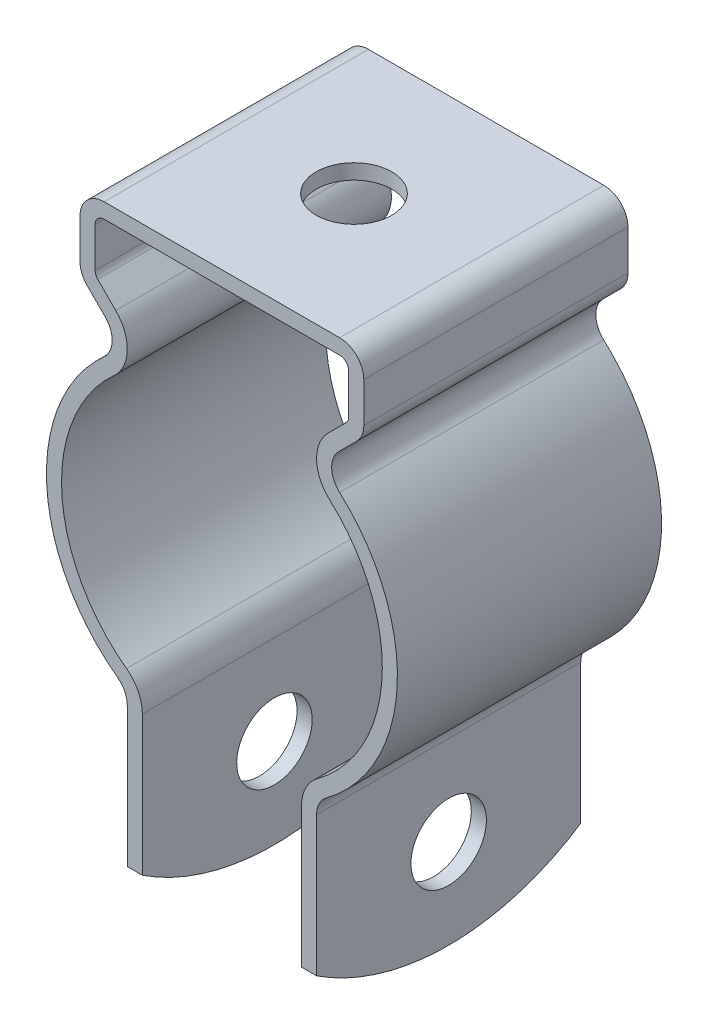
SolidWorks part; units mm, degrees
ref_plane "Front" through (0, 0, 0) normal (0, 0, 1) x (1, 0, 0)
ref_plane "Top" through (0, 0, 0) normal (0, 1, 0) x (1, 0, 0)
ref_plane "Right" through (0, 0, 0) normal (1, 0, 0) x (0, 0, -1)
sketch "Sketch1" plane through (0, 0, 0) normal (0, 0, 1) x (1, 0, 0)
  line L0 (-11.3428, 15.4065) -> (-9.8296, 13.8933) construction
  line L1 (-11.938, 16.8434) -> (-11.938, 20.193) construction
  line L2 (-9.906, 22.225) -> (9.906, 22.225) construction
  line L3 (11.938, 20.193) -> (11.938, 16.8434) construction
  line L4 (11.3428, 15.4065) -> (9.8296, 13.8933) construction
  line L5 (-7.9645, -13.497) -> (-7.9645, -28.575) construction
  line L6 (6.6945, -28.575) -> (6.6945, -13.497) construction
  line L7 (7.9645, -28.575) -> (7.9645, -13.497) construction
  line L8 (10.4448, 16.3046) -> (8.9316, 14.7913) construction
  line L9 (10.668, 20.193) -> (10.668, 16.8434) construction
  line L10 (-9.906, 20.955) -> (9.906, 20.955) construction
  line L11 (-10.668, 16.8434) -> (-10.668, 20.193) construction
  line L12 (-10.4448, 16.3046) -> (-8.9316, 14.7913) construction
  line L13 (-6.6945, -13.497) -> (-6.6945, -28.575) construction
  line L14 (-7.9645, -28.575) -> (-6.6945, -28.575) construction
  line L15 (6.6945, -28.575) -> (7.9645, -28.575) construction
  line L16 (0, 16.8434) -> (0, 13.4937) construction
  line L17 (-11.938, 16.8434) -> (0, 16.8434) construction
  line L18 (7.9645, -24.211) -> (7.9645, -17.861) construction
  arc A0 (-9.9034, 10.9495) -> (-8.7871, -11.8641) centre (0, 0) ccw construction
  arc A1 (-9.8296, 13.8933) -> (-9.9034, 10.9495) centre (-11.2665, 12.4565) cw construction
  arc A2 (9.8296, 13.8933) -> (9.9034, 10.9495) centre (11.2665, 12.4565) ccw construction
  arc A3 (8.7871, -11.8641) -> (9.9034, 10.9495) centre (0, 0) ccw construction
  arc A4 (8.7871, -11.8641) -> (7.9645, -13.497) centre (9.9965, -13.497) ccw construction
  arc A5 (-7.9645, -13.497) -> (-8.7871, -11.8641) centre (-9.9965, -13.497) ccw construction
  arc A6 (11.3428, 15.4065) -> (11.938, 16.8434) centre (9.906, 16.8434) ccw construction
  arc A7 (11.938, 20.193) -> (9.906, 22.225) centre (9.906, 20.193) ccw construction
  arc A8 (-11.3428, 15.4065) -> (-11.938, 16.8434) centre (-9.906, 16.8434) cw construction
  arc A9 (-11.938, 20.193) -> (-9.906, 22.225) centre (-9.906, 20.193) cw construction
  arc A10 (8.0312, -10.8435) -> (6.6945, -13.497) centre (9.9965, -13.497) ccw construction
  arc A11 (8.0312, -10.8435) -> (9.0515, 10.0076) centre (0, 0) ccw construction
  arc A12 (8.9316, 14.7913) -> (9.0515, 10.0076) centre (11.2665, 12.4565) ccw construction
  arc A13 (10.4448, 16.3046) -> (10.668, 16.8434) centre (9.906, 16.8434) ccw construction
  arc A14 (10.668, 20.193) -> (9.906, 20.955) centre (9.906, 20.193) ccw construction
  arc A15 (-10.668, 20.193) -> (-9.906, 20.955) centre (-9.906, 20.193) cw construction
  arc A16 (-10.4448, 16.3046) -> (-10.668, 16.8434) centre (-9.906, 16.8434) cw construction
  arc A17 (-8.9316, 14.7913) -> (-9.0515, 10.0076) centre (-11.2665, 12.4565) cw construction
  arc A18 (-9.0515, 10.0076) -> (-8.0312, -10.8435) centre (0, 0) ccw construction
  arc A19 (-6.6945, -13.497) -> (-8.0312, -10.8435) centre (-9.9965, -13.497) ccw construction
  point P1 (0, 22.225)
  point P59 (-14.7461, -0.7216)
  point P60 (14.7461, -0.7216)
  point P64 (7.9645, -21.036)
  point P65 (7.9645, -17.861)
  dimension "D2" = 2.032
  dimension "ID" = 26.9875
  dimension "Top Length" = 23.876
  dimension "Center-to-Top" = 22.225
  dimension "D1" = 45
  dimension "Height" = 50.8
  dimension "Length" = 29.4922
  dimension "For Screw Diameter" = 6.35
  dimension "Thickness" = 1.27
sketch "Sketch2" plane through (0, 0, 0) normal (0, 1, 0) x (1, 0, 0)
  line L0 (0, -11.1125) -> (0, 11.1125) construction
  circle A0 centre (0, 0) radius 3.175 construction
  point P6 (0, 0)
  dimension "Mounting Hole Diameter" = 6.35
  dimension "Width" = 22.225
sketch "Sketch3" plane through (0, 0, 0) normal (0, 0, 1) x (1, 0, 0)
  line L0 (-10.668, 16.8434) -> (-10.668, 20.193) construction
  line L1 (-11.938, 16.8434) -> (-11.938, 20.193) construction
  line L2 (-10.4448, 16.3046) -> (-8.9316, 14.7913) construction
  line L3 (-11.3428, 15.4065) -> (-9.8296, 13.8933) construction
  line L4 (-10.668, 16.8434) -> (-10.668, 20.193)
  line L5 (-11.938, 16.8434) -> (-11.938, 20.193)
  line L6 (-10.4448, 16.3046) -> (-8.9316, 14.7913)
  line L7 (-11.3428, 15.4065) -> (-9.8296, 13.8933)
  line L8 (-9.906, 22.225) -> (9.906, 22.225)
  line L9 (-9.906, 22.225) -> (9.906, 22.225) construction
  line L10 (0, 22.225) -> (0, 0) construction
  line L11 (-9.906, 20.955) -> (9.906, 20.955)
  line L12 (-9.906, 20.955) -> (9.906, 20.955) construction
  line L13 (-7.9645, -28.575) -> (-6.6945, -28.575) construction
  line L14 (-6.6945, -13.497) -> (-6.6945, -28.575) construction
  line L15 (-7.9645, -13.497) -> (-7.9645, -28.575) construction
  line L16 (-7.9645, -28.575) -> (-6.6945, -28.575)
  line L17 (-6.6945, -13.497) -> (-6.6945, -28.575)
  line L18 (-7.9645, -13.497) -> (-7.9645, -28.575)
  line L19 (7.9645, -13.497) -> (7.9645, -28.575)
  line L20 (6.6945, -13.497) -> (6.6945, -28.575)
  line L21 (7.9645, -28.575) -> (6.6945, -28.575)
  line L22 (11.3428, 15.4065) -> (9.8296, 13.8933)
  line L23 (10.4448, 16.3046) -> (8.9316, 14.7913)
  line L24 (11.938, 16.8434) -> (11.938, 20.193)
  line L25 (10.668, 16.8434) -> (10.668, 20.193)
  arc A0 (-9.906, 22.225) -> (-11.938, 20.193) centre (-9.906, 20.193) ccw construction
  arc A1 (-9.906, 20.955) -> (-10.668, 20.193) centre (-9.906, 20.193) ccw construction
  arc A2 (-11.938, 16.8434) -> (-11.3428, 15.4065) centre (-9.906, 16.8434) ccw construction
  arc A3 (-10.668, 16.8434) -> (-10.4448, 16.3046) centre (-9.906, 16.8434) ccw construction
  arc A4 (-9.9034, 10.9495) -> (-9.8296, 13.8933) centre (-11.2665, 12.4565) ccw construction
  arc A5 (-9.0515, 10.0076) -> (-8.9316, 14.7913) centre (-11.2665, 12.4565) ccw construction
  arc A6 (-9.0515, 10.0076) -> (-8.0312, -10.8435) centre (0, 0) ccw construction
  arc A7 (-9.9034, 10.9495) -> (-8.7871, -11.8641) centre (0, 0) ccw construction
  arc A8 (-9.906, 22.225) -> (-11.938, 20.193) centre (-9.906, 20.193) ccw
  arc A9 (-9.906, 20.955) -> (-10.668, 20.193) centre (-9.906, 20.193) ccw
  arc A10 (-11.938, 16.8434) -> (-11.3428, 15.4065) centre (-9.906, 16.8434) ccw
  arc A11 (-10.668, 16.8434) -> (-10.4448, 16.3046) centre (-9.906, 16.8434) ccw
  arc A12 (-9.9034, 10.9495) -> (-9.8296, 13.8933) centre (-11.2665, 12.4565) ccw
  arc A13 (-9.0515, 10.0076) -> (-8.9316, 14.7913) centre (-11.2665, 12.4565) ccw
  arc A14 (-9.0515, 10.0076) -> (-8.0312, -10.8435) centre (0, 0) ccw
  arc A15 (-9.9034, 10.9495) -> (-8.7871, -11.8641) centre (0, 0) ccw
  arc A16 (-6.6945, -13.497) -> (-8.0312, -10.8435) centre (-9.9965, -13.497) ccw construction
  arc A17 (-7.9645, -13.497) -> (-8.7871, -11.8641) centre (-9.9965, -13.497) ccw construction
  arc A18 (-6.6945, -13.497) -> (-8.0312, -10.8435) centre (-9.9965, -13.497) ccw
  arc A19 (-7.9645, -13.497) -> (-8.7871, -11.8641) centre (-9.9965, -13.497) ccw
  arc A20 (7.9645, -13.497) -> (8.7871, -11.8641) centre (9.9965, -13.497) cw
  arc A21 (6.6945, -13.497) -> (8.0312, -10.8435) centre (9.9965, -13.497) cw
  arc A22 (9.9034, 10.9495) -> (8.7871, -11.8641) centre (0, 0) cw
  arc A23 (9.0515, 10.0076) -> (8.0312, -10.8435) centre (0, 0) cw
  arc A24 (9.0515, 10.0076) -> (8.9316, 14.7913) centre (11.2665, 12.4565) cw
  arc A25 (9.9034, 10.9495) -> (9.8296, 13.8933) centre (11.2665, 12.4565) cw
  arc A26 (10.668, 16.8434) -> (10.4448, 16.3046) centre (9.906, 16.8434) cw
  arc A27 (11.938, 16.8434) -> (11.3428, 15.4065) centre (9.906, 16.8434) cw
  arc A28 (9.906, 20.955) -> (10.668, 20.193) centre (9.906, 20.193) cw
  arc A29 (9.906, 22.225) -> (11.938, 20.193) centre (9.906, 20.193) cw
  point P51 (0, 20.955)
extrude "Boss-Extrude1" add sketch "Sketch3" along normal up to vertex (11.1125 mm away) and the other way up to vertex (11.1125 mm away) up to point (0, 0, 11.1125) other way up to point (0, 0, -11.1125)
sketch "Sketch4" plane through (0, 22.225, 0) normal (0, 1, 0) x (1, 0, 0)
  circle A0 centre (0, 0) radius 3.175 construction
  circle A1 centre (0, 0) radius 3.175
extrude "Cut-Extrude1" cut sketch "Sketch4" against normal up to vertex (22.225 mm away) up to point (0, 0, 0)
sketch "Sketch5" plane through (0, 0, 0) normal (1, 0, 0) x (0, 0, -1)
  line L0 (0, -13.497) -> (0, -28.575) construction
  line L1 (0, -13.497) -> (0, -28.575) construction
  line L2 (-11.1125, 0) -> (11.1125, 0) construction
  line L3 (-11.1125, 0) -> (11.1125, 0) construction
  line L4 (-11.1125, -25.2412) -> (-11.1125, -31.9087)
  line L5 (-11.1125, -31.9087) -> (11.1125, -31.9087)
  line L6 (11.1125, -31.9087) -> (11.1125, -25.2412)
  line L7 (-11.1125, -28.575) -> (11.1125, -28.575) construction
  arc A0 (-11.1125, -25.2412) -> (11.1125, -25.2412) centre (0, -8.3873) ccw
  point P6 (0, -28.575)
  point P13 (-11.1125, -28.575)
  dimension "D1" = 3.3337
extrude "Cut-Extrude2" cut sketch "Sketch5" against normal through all both and the other way through all
sketch "Sketch6" plane through (0, 0, 0) normal (1, 0, 0) x (0, 0, -1)
  circle A0 centre (0, -21.036) radius 3.175
  point P0 (0, -17.861)
  point P2 (0, -21.036)
extrude "Cut-Extrude3" cut sketch "Sketch6" against normal through all both and the other way through all
sketch "Sketch7" plane through (0, 0, 0) normal (0, 0, 1) x (1, 0, 0)
  line L0 (-7.9645, -24.211) -> (-6.6945, -24.211)
  line L1 (-6.6945, -17.861) -> (-7.9645, -17.861)
  line L2 (-6.6945, -17.861) -> (-7.9645, -17.861)
  line L3 (-7.9645, -24.211) -> (-6.6945, -24.211)
  line L4 (6.6945, -24.211) -> (7.9645, -24.211)
  line L5 (7.9645, -17.861) -> (6.6945, -17.861)
  line L6 (7.9645, -17.861) -> (6.6945, -17.861)
  line L7 (6.6945, -24.211) -> (7.9645, -24.211)
equation "\"D2@Sketch1\" = \"Thickness@Sketch1\" * 1.6"
equation "\"D1@Sketch5\"=\"Width@Sketch2\"*.15"
equation "\"D1\" = \"D4\" * .75"
